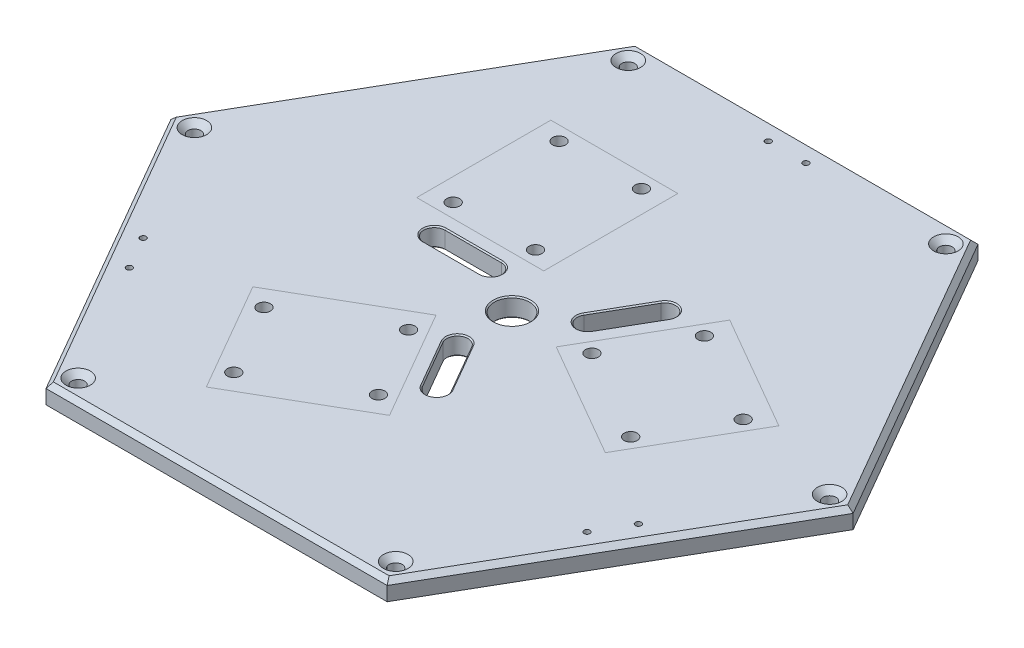
SolidWorks part; units mm, degrees
material "5052-H32"
ref_plane "Front Plane" through (0, 0, 0) normal (0, 0, 1) x (1, 0, 0)
ref_plane "Top Plane" through (0, 0, 0) normal (0, 1, 0) x (1, 0, 0)
ref_plane "Right Plane" through (0, 0, 0) normal (1, 0, 0) x (0, 0, -1)
sketch "Sketch1" plane through (0, 0, 0) normal (0, 1, 0) x (1, 0, 0)
  line L1 (72.5, 125.5737) -> (-72.5, 125.5737)
  line L2 (-72.5, 125.5737) -> (-145, 0)
  line L3 (-145, 0) -> (-72.5, -125.5737)
  line L4 (-72.5, -125.5737) -> (72.5, -125.5737)
  line L5 (72.5, -125.5737) -> (145, 0)
  line L6 (145, 0) -> (72.5, 125.5737)
  circle A0 centre (0, 0) radius 125.5737 construction
  dimension "D1" = 145
extrude "Boss-Extrude1" add sketch "Sketch1" along normal blind 8
sketch "Sketch2" plane through (0, 0, 0) normal (0, 1, 0) x (1, 0, 0)
  line L0 (0, 0) -> (108.75, 62.7868) construction
  line L1 (145, 0) -> (72.5, 125.5737) construction
  line L2 (69.5513, 20.4663) -> (52.0513, -9.8446) construction
  line L3 (69.0368, -25.4247) -> (30.0657, -2.9247) construction
  line L4 (66.5368, -29.7548) -> (27.5657, -7.2548) construction
  line L5 (53.4484, -16.4247) -> (43.4484, -33.7452) construction
  line L6 (32.5657, 1.4054) -> (71.5368, -21.0946) construction
  line L7 (71.5368, -21.0946) -> (89.0368, 9.2163) construction
  line L8 (89.0368, 9.2163) -> (50.0657, 31.7163) construction
  line L9 (50.0657, 31.7163) -> (32.5657, 1.4054) construction
  line L10 (-15.0657, -28.9054) -> (-54.0368, -51.4054) construction
  line L11 (2.4343, -59.2163) -> (-15.0657, -28.9054) construction
  line L12 (-36.5368, -81.7163) -> (2.4343, -59.2163) construction
  line L13 (-54.0368, -51.4054) -> (-36.5368, -81.7163) construction
  line L14 (-17.5, 27.5) -> (-17.5, 72.5) construction
  line L15 (-52.5, 27.5) -> (-17.5, 27.5) construction
  line L16 (-52.5, 72.5) -> (-52.5, 27.5) construction
  line L17 (-17.5, 72.5) -> (-52.5, 72.5) construction
  line L18 (43.4484, -33.7452) -> (35.6542, -29.2452) construction
  line L19 (52.0513, -9.8446) -> (43.3013, -25) construction
  line L20 (35.6542, -29.2452) -> (43.1542, -16.2548) construction
  line L21 (108.75, -62.7868) -> (0, 0) construction
  line L22 (72.5, -125.5737) -> (145, 0) construction
  point P9 (49.5513, -14.1747)
  point P18 (32.5657, 1.4054)
  point P19 (50.0657, 31.7163)
  point P20 (89.0368, 9.2163)
  point P21 (71.5368, -21.0946)
  point P31 (0, 0)
  point P33 (47.0513, -18.5048)
  point P36 (39.5513, -31.4952)
  point P39 (39.4042, -22.75)
  dimension "D1" = 45
  dimension "D2" = 35
  dimension "D4" = 5
  dimension "D5" = 5
  dimension "D6" = 50
  dimension "D7" = 20
  dimension "D8" = 9
  dimension "D3" = 3
sketch "Sketch5" plane through (0, 8, 0) normal (0, 1, 0) x (1, 0, 0)
  circle A0 centre (0, 0) radius 7.5
  dimension "D1" = 15
extrude "Cut-Extrude1" cut sketch "Sketch5" against normal through all
hole_wizard "CSK for M5 Flat Head Machine Screw1" positions "Sketch7" profile "Sketch6" countersink size "M5" standard "ANSI Metric" end condition through all
sketch "Sketch7" plane through (0, 0, 0) normal (0, -1, 0) x (-1, 0, 0)
  point P0 (52.5, 27.5)
  point P3 (17.5, 27.5)
  point P6 (17.5, 72.5)
  point P9 (52.5, 72.5)
  point P12 (-32.5657, 1.4054)
  point P15 (-71.5368, -21.0946)
  point P18 (-89.0368, 9.2163)
  point P21 (-50.0657, 31.7163)
  point P24 (15.0657, -28.9054)
  point P27 (-2.4343, -59.2163)
  point P30 (36.5368, -81.7163)
  point P33 (54.0368, -51.4054)
sketch "Sketch6" plane through (-52.5, 0, -27.5) normal (1, 0, 0) x (0, 0, -1)
  line L0 (0, 0) -> (0, 8)
  line L1 (0, 8) -> (2.75, 8)
  line L2 (2.75, 8) -> (2.75, 2.45)
  line L3 (2.75, 2.45) -> (5.2, 0)
  line L5 (5.2, 0) -> (0, 0)
  line L6 (-2.75, 2.45) -> (-5.2, 0) construction
  line L11 (0, -6.35) -> (0, 107.95) construction
  dimension "Thru Hole Dia." = 5.5
  dimension "Thru Hole Depth" = 8
  dimension "Near C'Sink Dia." = 10.4
  dimension "Near C'Sink Angle" = 90
sketch "Sketch9" plane through (0, 0, 0) normal (0, -1, 0) x (1, 0, 0)
  line L0 (32.2093, -32.7881) -> (20.2093, -12.0035) construction
  line L1 (28.3122, -35.0381) -> (16.3122, -14.2535)
  line L2 (36.1064, -30.5381) -> (24.1064, -9.7535)
  line L3 (18.7093, -9.4054) -> (36.2093, -39.7163) construction
  line L4 (89.0368, -9.2163) -> (50.0657, -31.7163) construction
  line L5 (32.5657, -1.4054) -> (71.5368, 21.0946) construction
  line L6 (50.0657, -31.7163) -> (32.5657, -1.4054) construction
  line L7 (-44.5, -11.5) -> (-20.5, -11.5) construction
  line L8 (-44.5, -7) -> (-20.5, -7)
  line L9 (-44.5, -16) -> (-20.5, -16)
  line L10 (12.2907, 44.2881) -> (0.2907, 23.5035) construction
  line L11 (16.1878, 42.0381) -> (4.1878, 21.2535)
  line L12 (8.3936, 46.5381) -> (-3.6064, 25.7535)
  line L13 (36.2093, -39.7163) -> (50.0657, -31.7163) construction
  arc A0 (28.3122, -35.0381) -> (36.1064, -30.5381) centre (32.2093, -32.7881) ccw
  arc A1 (24.1064, -9.7535) -> (16.3122, -14.2535) centre (20.2093, -12.0035) ccw
  arc A2 (-44.5, -7) -> (-44.5, -16) centre (-44.5, -11.5) ccw
  arc A3 (-20.5, -16) -> (-20.5, -7) centre (-20.5, -11.5) ccw
  arc A4 (16.1878, 42.0381) -> (8.3936, 46.5381) centre (12.2907, 44.2881) ccw
  arc A5 (-3.6064, 25.7535) -> (4.1878, 21.2535) centre (0.2907, 23.5035) ccw
  point P2 (26.2093, -22.3958)
  point P19 (-32.5, -11.5)
  point P26 (6.2907, 33.8958)
  point P31 (0, 0)
  dimension "D1" = 16
  dimension "D2" = 9
  dimension "D3" = 24
  dimension "D5" = 20
  dimension "D4" = 3
extrude "Cut-Extrude3" cut sketch "Sketch9" against normal through all
sketch "Sketch10" plane through (0, 8, 0) normal (0, 1, 0) x (1, 0, 0)
  line L0 (145, 0) -> (0, 0) construction
  point P4 (135, 0)
  point P7 (67.5, -116.9134)
  point P8 (-67.5, -116.9134)
  point P9 (-135, 0)
  point P10 (-67.5, 116.9134)
  point P11 (67.5, 116.9134)
  point P12 (0, 0)
  dimension "D2" = 10
  dimension "D1" = 6
hole_wizard "CSK for M5 Flat Head Machine Screw2" positions "Sketch14" profile "Sketch13" countersink size "M5" standard "ANSI Metric"
sketch "Sketch14" plane through (0, 8, 0) normal (0, 1, 0) x (1, 0, 0)
  point P0 (-135, 0)
  point P3 (-67.5, -116.9134)
  point P6 (67.5, -116.9134)
  point P9 (135, 0)
  point P12 (67.5, 116.9134)
  point P15 (-67.5, 116.9134)
sketch "Sketch13" plane through (-135, 8, 0) normal (1, 0, 0) x (0, 0, 1)
  line L0 (0, 0) -> (0, 11.6524)
  line L1 (0, 11.6524) -> (2.75, 10)
  line L2 (2.75, 10) -> (2.75, 2.45)
  line L3 (2.75, 2.45) -> (5.2, 0)
  line L5 (5.2, 0) -> (0, 0)
  line L6 (-2.75, 2.45) -> (-5.2, 0) construction
  line L10 (0, 11.6524) -> (-2.75, 10) construction
  line L11 (0, -6.35) -> (0, 107.95) construction
  dimension "Hole Dia." = 5.5
  dimension "Hole Depth" = 10
  dimension "Near C'Sink Dia." = 10.4
  dimension "Near C'Sink Angle" = 90
  dimension "Drill Angle" = 118
chamfer "Chamfer1" distance 0.5 angle 45 24 edges at (-32.5, 0, -16) (-16, 0, -11.5) (-49, 0, -11.5) (-32.5, 0, -7) (22.3122, 0, -24.6458) (34.4593, 0, -36.6852) (17.9593, 0, -8.1064) (30.1064, 0, -20.1458) (2.3936, 0, 36.1458) (-1.9593, 0, 19.6064) (14.5407, 0, 48.1852) (10.1878, 0, 31.6458) (-32.5, 8, -16) (-16, 8, -11.5) (-49, 8, -11.5) (-32.5, 8, -7) (22.3122, 8, -24.6458) (34.4593, 8, -36.6852) (17.9593, 8, -8.1064) (30.1064, 8, -20.1458) (2.3936, 8, 36.1458) (-1.9593, 8, 19.6064) (14.5407, 8, 48.1852) (10.1878, 8, 31.6458)
sketch "Sketch8" plane through (0, 0, 0) normal (0, -1, 0) x (1, 0, 0)
  line L0 (104.25, 70.5811) -> (113.25, 54.9926)
  line L1 (104.25, 70.5811) -> (66.9471, 49.0442)
  line L2 (113.25, 54.9926) -> (75.9471, 33.4558)
  line L3 (66.9471, 49.0442) -> (75.9471, 33.4558)
  line L4 (72.5, 125.5737) -> (145, 0) construction
  line L5 (108.75, 62.7868) -> (0, 0) construction
  line L7 (9, -125.5737) -> (-9, -125.5737)
  line L8 (9, -125.5737) -> (9, -82.5)
  line L9 (-9, -125.5737) -> (-9, -82.5)
  line L10 (9, -82.5) -> (-9, -82.5)
  line L11 (-113.25, 54.9926) -> (-104.25, 70.5811)
  line L12 (-113.25, 54.9926) -> (-75.9471, 33.4558)
  line L13 (-104.25, 70.5811) -> (-66.9471, 49.0442)
  line L14 (-75.9471, 33.4558) -> (-66.9471, 49.0442)
  circle A0 centre (0, 0) radius 7.5 construction
  point P6 (108.75, 62.7868)
  point P22 (0, 0)
  dimension "D1" = 18
  dimension "D2" = 10
  dimension "D3" = 3
extrude "Cut-Extrude2" [suppressed] cut sketch "Sketch8" against normal through all
chamfer "Chamfer3" distance 0.5 angle 45 2 edges at (0, 8, 7.5) (0, 0, 7.5)
chamfer "Chamfer4" distance 2 angle 45 6 edges at (0, 8, 125.5737) (108.75, 8, 62.7868) (108.75, 8, -62.7868) (0, 8, -125.5737) (-108.75, 8, -62.7868) (-108.75, 8, 62.7868)
sketch "Sketch15" plane through (0, 8, 0) normal (0, 1, 0) x (1, 0, 0)
  line L0 (0, 0) -> (107.0179, -61.7868) construction
  line L1 (71.3453, -123.5737) -> (142.6906, 0) construction
  line L2 (97.25, -65.3849) -> (105.25, -51.5285) construction
  circle A0 centre (97.25, -65.3849) radius 1.5
  circle A1 centre (105.25, -51.5285) radius 1.5
  circle A2 centre (-105.25, -51.5285) radius 1.5
  circle A3 centre (-97.25, -65.3849) radius 1.5
  circle A4 centre (8, 116.9134) radius 1.5
  circle A5 centre (-8, 116.9134) radius 1.5
  circle A6 centre (67.5, -116.9134) radius 2.75 construction
  point P7 (101.25, -58.4567)
  point P21 (0, 0)
  dimension "D2" = 3
  dimension "D1" = 16
  dimension "D4" = 0
  dimension "D3" = 3
hole_wizard "M3x0.5 Tapped Hole1" positions "Sketch17" profile "Sketch16" tap size "M3x0.5" standard "ANSI Metric" end condition through all
sketch "Sketch17" plane through (0, 8, 0) normal (0, 1, 0) x (1, 0, 0)
  point P0 (97.25, -65.3849)
  point P3 (105.25, -51.5285)
  point P6 (8, 116.9134)
  point P9 (-8, 116.9134)
  point P12 (-105.25, -51.5285)
  point P15 (-97.25, -65.3849)
sketch "Sketch16" plane through (97.25, 8, 65.3849) normal (1, 0, 0) x (0, 0, 1)
  line L0 (0, 0) -> (0, 8)
  line L1 (0, 8) -> (1.25, 8)
  line L2 (1.25, 8) -> (1.25, 0)
  line L5 (1.25, 0) -> (0, 0)
  line L11 (0, -6.35) -> (0, 107.95) construction
  dimension "Thru Tap Drill Dia." = 2.5
  dimension "Thru Tap Drill Depth" = 8
cosmetic thread "Hole Thread1" parameters "D2"=3
cosmetic thread "Hole Thread2" parameters "D2"=3
cosmetic thread "Hole Thread3" parameters "D2"=3
cosmetic thread "Hole Thread4" parameters "D2"=3
cosmetic thread "Hole Thread5" parameters "D2"=3
cosmetic thread "Hole Thread6" parameters "D2"=3
sketch "Sketch22" plane through (0, 0, 0) normal (0, -1, 0) x (1, 0, 0)
  line L0 (72.5, 125.5737) -> (75, 121.2436)
  line L1 (72.5, 125.5737) -> (145, 0) construction
  line L2 (75, 121.2436) -> (73.2679, 120.2436)
  line L3 (73.2679, 120.2436) -> (78.2679, 111.5833)
  line L4 (78.2679, 111.5833) -> (76.2501, 110.4183)
  line L5 (76.2501, 110.4183) -> (65, 112.5833)
  line L6 (72.5, 125.5737) -> (65, 112.5833) construction
  line L7 (72.5, 125.5737) -> (67.5, 125.5737)
  line L8 (67.5, 125.5737) -> (67.5, 123.5737)
  line L9 (67.5, 123.5737) -> (57.5, 123.5737)
  line L10 (57.5, 123.5737) -> (57.5, 121.2437)
  line L11 (57.5, 121.2437) -> (65, 112.5833)
  line L12 (145, 0) -> (142.5, -4.3301)
  line L13 (142.5, -4.3301) -> (140.7679, -3.3301)
  line L14 (140.7679, -3.3301) -> (135.7679, -11.9904)
  line L15 (135.7679, -11.9904) -> (133.7501, -10.8254)
  line L16 (133.7501, -10.8254) -> (130, 0)
  line L17 (145, 0) -> (142.5, 4.3301)
  line L18 (142.5, 4.3301) -> (140.7679, 3.3301)
  line L19 (140.7679, 3.3301) -> (135.7679, 11.9904)
  line L20 (135.7679, 11.9904) -> (133.7501, 10.8254)
  line L21 (133.7501, 10.8254) -> (130, 0)
  line L22 (145, 0) -> (130, 0) construction
  line L23 (72.5, -125.5737) -> (67.5, -125.5737)
  line L24 (67.5, -125.5737) -> (67.5, -123.5737)
  line L25 (67.5, -123.5737) -> (57.5, -123.5737)
  line L26 (57.5, -123.5737) -> (57.5, -121.2437)
  line L27 (57.5, -121.2437) -> (65, -112.5833)
  line L28 (72.5, -125.5737) -> (75, -121.2436)
  line L29 (75, -121.2436) -> (73.2679, -120.2436)
  line L30 (73.2679, -120.2436) -> (78.2679, -111.5833)
  line L31 (78.2679, -111.5833) -> (76.2501, -110.4183)
  line L32 (76.2501, -110.4183) -> (65, -112.5833)
  line L33 (72.5, -125.5737) -> (65, -112.5833) construction
  line L34 (-72.5, -125.5737) -> (-75, -121.2436)
  line L35 (-75, -121.2436) -> (-73.2679, -120.2436)
  line L36 (-73.2679, -120.2436) -> (-78.2679, -111.5833)
  line L37 (-78.2679, -111.5833) -> (-76.2501, -110.4183)
  line L38 (-76.2501, -110.4183) -> (-65, -112.5833)
  line L39 (-72.5, -125.5737) -> (-67.5, -125.5737)
  line L40 (-67.5, -125.5737) -> (-67.5, -123.5737)
  line L41 (-67.5, -123.5737) -> (-57.5, -123.5737)
  line L42 (-57.5, -123.5737) -> (-57.5, -121.2437)
  line L43 (-57.5, -121.2437) -> (-65, -112.5833)
  line L44 (-72.5, -125.5737) -> (-65, -112.5833) construction
  line L45 (-145, 0) -> (-142.5, 4.3301)
  line L46 (-142.5, 4.3301) -> (-140.7679, 3.3301)
  line L47 (-140.7679, 3.3301) -> (-135.7679, 11.9904)
  line L48 (-135.7679, 11.9904) -> (-133.7501, 10.8254)
  line L49 (-133.7501, 10.8254) -> (-130, 0)
  line L50 (-145, 0) -> (-142.5, -4.3301)
  line L51 (-142.5, -4.3301) -> (-140.7679, -3.3301)
  line L52 (-140.7679, -3.3301) -> (-135.7679, -11.9904)
  line L53 (-135.7679, -11.9904) -> (-133.7501, -10.8254)
  line L54 (-133.7501, -10.8254) -> (-130, 0)
  line L55 (-145, 0) -> (-130, 0) construction
  line L56 (-72.5, 125.5737) -> (-67.5, 125.5737)
  line L57 (-67.5, 125.5737) -> (-67.5, 123.5737)
  line L58 (-67.5, 123.5737) -> (-57.5, 123.5737)
  line L59 (-57.5, 123.5737) -> (-57.5, 121.2437)
  line L60 (-57.5, 121.2437) -> (-65, 112.5833)
  line L61 (-72.5, 125.5737) -> (-75, 121.2436)
  line L62 (-75, 121.2436) -> (-73.2679, 120.2436)
  line L63 (-73.2679, 120.2436) -> (-78.2679, 111.5833)
  line L64 (-78.2679, 111.5833) -> (-76.2501, 110.4183)
  line L65 (-76.2501, 110.4183) -> (-65, 112.5833)
  line L66 (-72.5, 125.5737) -> (-65, 112.5833) construction
  point P5 (67.5, 116.9134)
  point P19 (135, 0)
  point P30 (67.5, -116.9134)
  point P41 (-67.5, -116.9134)
  point P52 (-135, 0)
  point P63 (-67.5, 116.9134)
  point P72 (0, 0)
  dimension "D1" = 5
  dimension "D2" = 2
  dimension "D3" = 10
  dimension "D4" = 15
  dimension "D5" = 2.33
  dimension "D6" = 6
split line "Split Line2"
sketch "Sketch23" plane through (0, 8, 0) normal (0, 1, 0) x (1, 0, 0)
  line L0 (-52.5, 72.5) -> (-17.5, 27.5) construction
  line L1 (98.983, 14.4436) -> (49.6195, 42.9436)
  line L2 (-62, 78.5) -> (-8, 78.5)
  line L3 (-62, 78.5) -> (-62, 21.5)
  line L4 (-62, 21.5) -> (-8, 21.5)
  line L5 (-8, 78.5) -> (-8, 21.5)
  line L6 (-62, 78.5) -> (-8, 21.5) construction
  line L7 (-62, 21.5) -> (-8, 78.5) construction
  line L8 (98.983, 14.4436) -> (71.983, -32.3218)
  line L9 (71.983, -32.3218) -> (22.6195, -3.8218)
  line L10 (49.6195, 42.9436) -> (22.6195, -3.8218)
  line L11 (-36.983, -92.9436) -> (12.3805, -64.4436)
  line L12 (-36.983, -92.9436) -> (-63.983, -46.1782)
  line L13 (-63.983, -46.1782) -> (-14.6195, -17.6782)
  line L14 (12.3805, -64.4436) -> (-14.6195, -17.6782)
  point P4 (-35, 50)
  point P20 (0, 0)
  dimension "D1" = 57
  dimension "D2" = 54
  dimension "D3" = 3
split line "Split Line3"
ref_axis "Axis5" through (74.3013, 8, -28.6936) along (-0.5, 0, 0.866)
ref_axis "Axis6" through (-12.3013, 8, 78.6936) along (-0.5, 0, -0.866)
ref_axis "Axis7" through (-8, 8, -50) along (-1, 0, 0)
sketch "Sketch31" plane through (0, 0, 0) normal (0, -1, 0) x (1, 0, 0)
  line L0 (-8, -116.9134) -> (8, -116.9134) construction
  line L1 (-8, -112.6634) -> (8, -112.6634)
  line L2 (54.6357, 116.9134) -> (62.3542, 108.0007)
  line L3 (-12.25, -116.9134) -> (-54.6357, -116.9134)
  line L4 (-54.6357, -116.9134) -> (-62.3542, -108.0007)
  line L5 (-62.3542, -108.0007) -> (-73.9321, -105.7726)
  line L6 (6.2285, 47.7881) -> (-5.7715, 27.0035)
  line L7 (6.3529, 20.0035) -> (18.3529, 40.7881)
  line L8 (-20.5, -4.5) -> (-44.5, -4.5)
  line L9 (-44.5, -18.5) -> (-20.5, -18.5)
  line L10 (-20.5, -4.5) -> (-44.5, -4.5)
  line L11 (-44.5, -18.5) -> (-20.5, -18.5)
  line L12 (38.2715, -29.2881) -> (26.2715, -8.5035)
  line L13 (14.1471, -15.5035) -> (26.1471, -36.2881)
  line L14 (-73.9321, -105.7726) -> (-128.5679, -11.1408)
  line L15 (-128.5679, -11.1408) -> (-124.7085, 0)
  line L16 (-57.5, -121.2437) -> (-65, -112.5833) construction
  line L17 (-65, -112.5833) -> (-76.2501, -110.4183) construction
  line L18 (-72.5, -125.5737) -> (-62.3542, -108.0007) construction
  line L19 (-145, 0) -> (-124.7085, 0) construction
  line L20 (-133.7501, -10.8254) -> (-130, 0) construction
  line L21 (12.25, -116.9134) -> (54.6357, -116.9134)
  line L22 (72.5, -125.5737) -> (62.3542, -108.0007) construction
  line L23 (54.6357, -116.9134) -> (62.3542, -108.0007)
  line L24 (65, -112.5833) -> (57.5, -121.2437) construction
  line L25 (-54.6357, 116.9134) -> (54.6357, 116.9134)
  line L26 (-62.3542, 108.0007) -> (-54.6357, 116.9134)
  line L27 (-73.9321, 105.7726) -> (-62.3542, 108.0007)
  line L28 (-95.125, 69.0655) -> (-73.9321, 105.7726)
  line L29 (-93.5694, 63.2599) -> (-101.5694, 49.4035)
  line L30 (-107.375, 47.8479) -> (-128.5679, 11.1408)
  line L31 (-128.5679, 11.1408) -> (-124.7085, 0)
  line L32 (73.9321, -105.7726) -> (62.3542, -108.0007)
  line L33 (128.5679, -11.1408) -> (73.9321, -105.7726)
  line L34 (124.7085, 0) -> (128.5679, -11.1408)
  line L35 (128.5679, 11.1408) -> (124.7085, 0)
  line L36 (107.375, 47.8479) -> (128.5679, 11.1408)
  line L37 (101.5694, 49.4035) -> (93.5694, 63.2599)
  line L38 (95.125, 69.0655) -> (73.9321, 105.7726)
  line L39 (73.9321, 105.7726) -> (62.3542, 108.0007)
  arc A0 (-8, -112.6634) -> (-12.25, -116.9134) centre (-8, -116.9134) ccw
  arc A1 (12.25, -116.9134) -> (8, -112.6634) centre (8, -116.9134) ccw
  circle A2 centre (-52.5, -27.5) radius 8.2
  circle A3 centre (-52.5, -27.5) radius 8.2
  circle A4 centre (-8, -116.9134) radius 1.25 construction
  circle A5 centre (-17.5, -27.5) radius 8.2
  circle A6 centre (-17.5, -27.5) radius 8.2
  circle A8 centre (-17.5, -72.5) radius 8.2
  circle A9 centre (-17.5, -72.5) radius 8.2
  arc A10 (-93.5694, 63.2599) -> (-95.125, 69.0655) centre (-97.25, 65.3849) ccw
  circle A11 centre (-52.5, -72.5) radius 8.2
  circle A12 centre (-52.5, -72.5) radius 8.2
  arc A13 (-107.375, 47.8479) -> (-101.5694, 49.4035) centre (-105.25, 51.5285) ccw
  arc A14 (101.5694, 49.4035) -> (107.375, 47.8479) centre (105.25, 51.5285) ccw
  arc A15 (95.125, 69.0655) -> (93.5694, 63.2599) centre (97.25, 65.3849) ccw
  circle A17 centre (2.4343, 59.2163) radius 8.2
  arc A18 (-20.5, -18.5) -> (-20.5, -4.5) centre (-20.5, -11.5) ccw
  arc A19 (-44.5, -4.5) -> (-44.5, -18.5) centre (-44.5, -11.5) ccw
  arc A20 (-20.5, -18.5) -> (-20.5, -4.5) centre (-20.5, -11.5) ccw
  arc A21 (-44.5, -4.5) -> (-44.5, -18.5) centre (-44.5, -11.5) ccw
  circle A22 centre (0, 0) radius 11
  circle A23 centre (0, 0) radius 11
  circle A24 centre (-15.0657, 28.9054) radius 8.2
  circle A25 centre (-54.0368, 51.4054) radius 8.2
  circle A26 centre (-36.5368, 81.7163) radius 8.2
  arc A27 (18.3529, 40.7881) -> (6.2285, 47.7881) centre (12.2907, 44.2881) ccw
  arc A28 (-5.7715, 27.0035) -> (6.3529, 20.0035) centre (0.2907, 23.5035) ccw
  circle A29 centre (50.0657, -31.7163) radius 8.2
  circle A30 centre (32.5657, -1.4054) radius 8.2
  circle A31 centre (71.5368, 21.0946) radius 8.2
  circle A32 centre (89.0368, -9.2163) radius 8.2
  arc A33 (26.1471, -36.2881) -> (38.2715, -29.2881) centre (32.2093, -32.7881) ccw
  arc A34 (26.2715, -8.5035) -> (14.1471, -15.5035) centre (20.2093, -12.0035) ccw
  point P51 (0, 0)
  point P52 (0, -115.9719)
  point P57 (0, -112.6634)
  point P115 (0, 0)
  dimension "D9" = 3
  dimension "D8" = 5
  dimension "D1" = 3
  dimension "D2" = 3
  dimension "D3" = 3
  dimension "D4" = 3
  dimension "D5" = 2
  dimension "D6" = 3
  dimension "D7" = 3
extrude "Cut-Extrude5" cut sketch "Sketch31" against normal blind 5 contours A15 L38 L39 L2 L25 L26 L27 L28 A10 L29 A13 L30 L31 L15 L14 L5 L4 L3 A0 L1 A1 L21 L23 L32 L33 L34 L35 L36 A14 L37 A34 L12 A33 L13 A32 A31 A30 A29 A28 L6 A27 L7 A26 region at (-13.4628, 0, -111.4506)
sketch "Sketch32" plane through (0, 5, 0) normal (0, -1, 0) x (1, 0, 0)
  line L0 (0, 0) -> (-124.7085, 0) construction
  line L1 (0, 0) -> (62.3542, -108.0007) construction
  line L2 (-16.936, -19.113) -> (-21.064, -19.887) construction
  line L3 (-16.8967, -19.3222) -> (-17.2054, -17.6762)
  line L4 (-20.5, -4.5) -> (-44.5, -4.5) construction
  line L5 (-44.5, -18.5) -> (-20.5, -18.5) construction
  line L6 (-52.5, -27.5) -> (-17.5, -72.5) construction
  line L7 (-17.5, -27.5) -> (-52.5, -72.5) construction
  line L8 (-41.4742, -54.9035) -> (-38.1589, -57.482) construction
  line L9 (-26.1968, -57.8979) -> (-29.512, -60.4765) construction
  line L10 (-49.2912, -35.0461) -> (-37.6604, -50)
  line L11 (-37.6604, -50) -> (-49.2912, -64.9539)
  line L12 (-45.9759, -67.5324) -> (-35, -53.4205)
  line L13 (-35, -53.4205) -> (-24.0241, -67.5324)
  line L14 (-47.0768, -21.3494) -> (-45.608, -18.4118)
  line L15 (-20.5, -11.5) -> (0, 0) construction
  line L16 (-20.7088, -64.9539) -> (-32.3396, -50)
  line L17 (-67.5, -116.9134) -> (-52.5, -72.5) construction
  line L18 (-67.5, -116.9134) -> (-17.5, -72.5) construction
  line L19 (-32.3396, -50) -> (-20.7088, -35.0461)
  line L20 (-24.0241, -32.4676) -> (-35, -46.5795)
  line L21 (-35, -46.5795) -> (-45.9759, -32.4676)
  line L22 (-44.5, -18.5) -> (-20.5, -18.5)
  line L23 (-20.5, -4.5) -> (-44.5, -4.5)
  line L24 (95.125, 69.0655) -> (73.9321, 105.7726)
  line L25 (73.9321, 105.7726) -> (62.3542, 108.0007)
  line L26 (62.3542, 108.0007) -> (54.6357, 116.9134)
  line L27 (54.6357, 116.9134) -> (-54.6357, 116.9134)
  line L28 (-54.6357, 116.9134) -> (-62.3542, 108.0007)
  line L29 (-62.3542, 108.0007) -> (-73.9321, 105.7726)
  line L30 (-73.9321, 105.7726) -> (-95.125, 69.0655)
  line L31 (-93.5694, 63.2599) -> (-101.5694, 49.4035)
  line L32 (-107.375, 47.8479) -> (-128.5679, 11.1408)
  line L33 (-128.5679, 11.1408) -> (-124.7085, 0)
  line L34 (-124.7085, 0) -> (-128.5679, -11.1408)
  line L35 (-128.5679, -11.1408) -> (-73.9321, -105.7726)
  line L36 (-73.9321, -105.7726) -> (-62.3542, -108.0007)
  line L37 (-62.3542, -108.0007) -> (-54.6357, -116.9134)
  line L38 (-54.6357, -116.9134) -> (-12.25, -116.9134)
  line L39 (-8, -112.6634) -> (8, -112.6634)
  line L40 (12.25, -116.9134) -> (54.6357, -116.9134)
  line L41 (54.6357, -116.9134) -> (62.3542, -108.0007)
  line L42 (62.3542, -108.0007) -> (73.9321, -105.7726)
  line L43 (73.9321, -105.7726) -> (128.5679, -11.1408)
  line L44 (128.5679, -11.1408) -> (124.7085, 0)
  line L45 (124.7085, 0) -> (128.5679, 11.1408)
  line L46 (128.5679, 11.1408) -> (107.375, 47.8479)
  line L47 (101.5694, 49.4035) -> (93.5694, 63.2599)
  line L48 (95.125, 69.0655) -> (73.9321, 105.7726)
  line L49 (73.9321, 105.7726) -> (62.3542, 108.0007)
  line L50 (62.3542, 108.0007) -> (54.6357, 116.9134)
  line L51 (54.6357, 116.9134) -> (-54.6357, 116.9134)
  line L52 (-54.6357, 116.9134) -> (-62.3542, 108.0007)
  line L53 (-62.3542, 108.0007) -> (-73.9321, 105.7726)
  line L54 (-73.9321, 105.7726) -> (-95.125, 69.0655)
  line L55 (-93.5694, 63.2599) -> (-101.5694, 49.4035)
  line L56 (-107.375, 47.8479) -> (-128.5679, 11.1408)
  line L57 (-128.5679, 11.1408) -> (-124.7085, 0)
  line L58 (-124.7085, 0) -> (-128.5679, -11.1408)
  line L59 (-128.5679, -11.1408) -> (-73.9321, -105.7726)
  line L60 (-73.9321, -105.7726) -> (-62.3542, -108.0007)
  line L61 (-62.3542, -108.0007) -> (-54.6357, -116.9134)
  line L62 (-54.6357, -116.9134) -> (-12.25, -116.9134)
  line L63 (-8, -112.6634) -> (8, -112.6634)
  line L64 (12.25, -116.9134) -> (54.6357, -116.9134)
  line L65 (54.6357, -116.9134) -> (62.3542, -108.0007)
  line L66 (62.3542, -108.0007) -> (73.9321, -105.7726)
  line L67 (73.9321, -105.7726) -> (128.5679, -11.1408)
  line L68 (128.5679, -11.1408) -> (124.7085, 0)
  line L69 (124.7085, 0) -> (128.5679, 11.1408)
  line L70 (128.5679, 11.1408) -> (107.375, 47.8479)
  line L71 (101.5694, 49.4035) -> (93.5694, 63.2599)
  line L72 (-57.0259, -79.3378) -> (-66.4408, -107.2143)
  line L73 (-53.0467, -80.6818) -> (-62.296, -108.0679)
  line L74 (-61.6038, -108.8672) -> (-24.8208, -76.194)
  line L75 (-22.0316, -79.3341) -> (-58.8541, -112.0424)
  line L76 (-41.1054, -96.2768) -> (-43.8946, -93.1367) construction
  line L77 (-61.9896, -94.0348) -> (-58.0104, -95.3787) construction
  line L78 (0, -112.6634) -> (-14.2245, -80.0174) construction
  line L79 (-5.1871, -95.5016) -> (-9.0374, -97.1793) construction
  line L80 (-16.2589, -80.6055) -> (-2.2907, -112.6634)
  line L81 (-12.4086, -78.9279) -> (2.2907, -112.6634)
  line L82 (-44.5, -11.5) -> (-52.5, -27.5) construction
  line L83 (-50.3783, -18.5609) -> (-46.6217, -20.4391) construction
  line L84 (-50.8334, -19.4711) -> (-49.3646, -16.5335)
  line L85 (-17.5, -27.5) -> (-20.5, -11.5) construction
  line L86 (-21.0248, -20.0962) -> (-21.3241, -18.5)
  line L87 (-8.3897, -7.1143) -> (-13.6488, -10.0645)
  line L88 (-10.4446, -3.4513) -> (-15.7036, -6.4015)
  line L89 (-11.2774, -3.9185) -> (-9.2226, -7.5815) construction
  line L90 (-17.5, -72.5) -> (20.2093, -12.0035) construction
  line L91 (-17.5, -27.5) -> (32.2093, -32.7881) construction
  line L93 (-0.4275, -41.1409) -> (3.1368, -43.3626) construction
  line L94 (0.3807, -27.2903) -> (-0.0636, -31.4668) construction
  line L96 (-9.3958, -26.2503) -> (7.7194, -28.071)
  line L97 (7.7194, -28.071) -> (14.8232, -16.6745)
  line L98 (14.1471, -15.5035) -> (26.1471, -36.2881) construction
  line L99 (17.203, -20.7964) -> (12.3607, -28.5648)
  line L100 (12.3607, -28.5648) -> (22.2984, -29.6219)
  line L101 (24.8965, -34.122) -> (9.8917, -32.5258)
  line L102 (9.8917, -32.5258) -> (-11.5249, -66.8841)
  line L103 (5.2503, -32.0321) -> (-15.0892, -64.6624)
  line L104 (5.2503, -32.0321) -> (-9.8401, -30.4267)
  line L107 (14.1471, -15.5035) -> (26.1471, -36.2881)
  arc A0 (-44.5, -4.5) -> (-44.5, -18.5) centre (-44.5, -11.5) ccw construction
  circle A1 centre (-52.5, -72.5) radius 8.2 construction
  circle A2 centre (-17.5, -72.5) radius 8.2 construction
  arc A3 (-20.5, -18.5) -> (-20.5, -4.5) centre (-20.5, -11.5) ccw construction
  arc A4 (-20.5, -18.5) -> (-20.5, -4.5) centre (-20.5, -11.5) ccw
  circle A5 centre (-17.5, -27.5) radius 8.2
  circle A6 centre (-17.5, -72.5) radius 8.2
  circle A7 centre (-17.5, -27.5) radius 8.2 construction
  arc A8 (26.1471, -36.2881) -> (38.2715, -29.2881) centre (32.2093, -32.7881) ccw
  circle A9 centre (-52.5, -27.5) radius 8.2 construction
  circle A10 centre (-52.5, -72.5) radius 8.2
  circle A11 centre (-52.5, -27.5) radius 8.2
  arc A12 (-44.5, -4.5) -> (-44.5, -18.5) centre (-44.5, -11.5) ccw
  arc A13 (95.125, 69.0655) -> (93.5694, 63.2599) centre (97.25, 65.3849) ccw
  arc A14 (-93.5694, 63.2599) -> (-95.125, 69.0655) centre (-97.25, 65.3849) ccw
  arc A15 (-107.375, 47.8479) -> (-101.5694, 49.4035) centre (-105.25, 51.5285) ccw
  arc A16 (-8, -112.6634) -> (-12.25, -116.9134) centre (-8, -116.9134) ccw
  arc A17 (12.25, -116.9134) -> (8, -112.6634) centre (8, -116.9134) ccw
  arc A18 (101.5694, 49.4035) -> (107.375, 47.8479) centre (105.25, 51.5285) ccw
  arc A19 (95.125, 69.0655) -> (93.5694, 63.2599) centre (97.25, 65.3849) ccw
  arc A20 (-93.5694, 63.2599) -> (-95.125, 69.0655) centre (-97.25, 65.3849) ccw
  arc A21 (-107.375, 47.8479) -> (-101.5694, 49.4035) centre (-105.25, 51.5285) ccw
  arc A22 (-8, -112.6634) -> (-12.25, -116.9134) centre (-8, -116.9134) ccw
  arc A23 (12.25, -116.9134) -> (8, -112.6634) centre (8, -116.9134) ccw
  arc A24 (101.5694, 49.4035) -> (107.375, 47.8479) centre (105.25, 51.5285) ccw
  circle A25 centre (0, 0) radius 11 construction
  circle A26 centre (0, 0) radius 11
  arc A27 (26.1471, -36.2881) -> (38.2715, -29.2881) centre (32.2093, -32.7881) ccw construction
  point P32 (-19, -19.5)
  point P61 (-39.8166, -56.1928)
  point P66 (-27.8544, -59.1872)
  point P104 (-42.5, -94.7067)
  point P107 (-60, -94.7067)
  point P109 (-7.1123, -96.3404)
  point P116 (-48.5, -19.5)
  point P122 (-10.25, -5.75)
  point P130 (1.3546, -42.2518)
  point P131 (0.1585, -29.3785)
  point P153 (1.3546, -42.2518)
  dimension "D2" = 4.2
  dimension "D1" = 0
extrude "Boss-Extrude4" add sketch "Sketch32" along normal up to surface (5 mm away) contours A11 L10 L11 A10 L12 L13 A6 L16 L19 A5 L20 L21 | A6 L102 L101 L107 L100 L99 L97 L96 A5 L104 L103 | A8 L81 A6 L80 L63 | A6 L74 L61 L75 | A10 L72 L60 L73 | A26 L88 A4 L87 | A5 L3 A4 L22 L86 | A12 L84 A11 L14 region at (-19.1071, 5, -18.9025) region at (3.2371, 5, -38.0628) region at (-12.0118, 5, -6.7383) region at (-35, 5, -50) region at (-48.2279, 5, -18.9558) region at (-41.8957, 5, -94.1704) region at (-7.1124, 5, -96.2952) region at (-59.7339, 5, -93.8973) up to face at (0, 0, 0)
pattern_circular "CirPattern5" count 3 over 360 about axis through (0, 0, 0) along (0, 1, 0) of "Boss-Extrude4"
